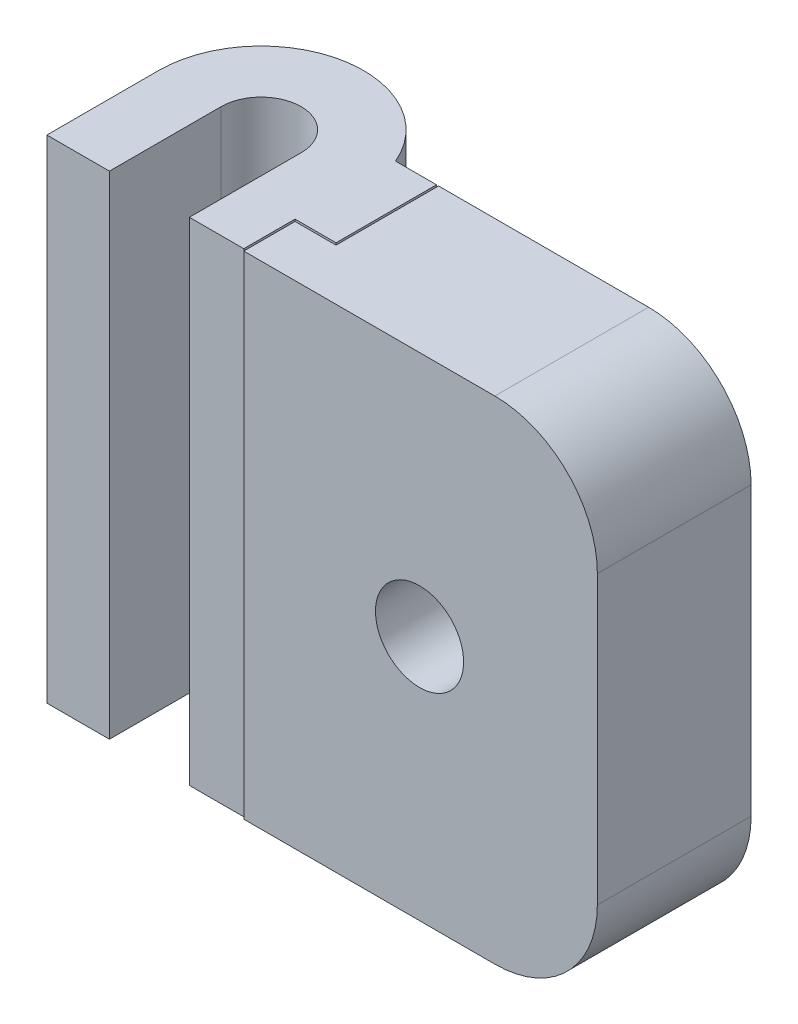
SolidWorks part; units mm, degrees
ref_plane "Front Plane" through (0, 0, 0) normal (0, 0, 1) x (1, 0, 0)
ref_plane "Top Plane" through (0, 0, 0) normal (0, 1, 0) x (1, 0, 0)
ref_plane "Right Plane" through (0, 0, 0) normal (1, 0, 0) x (0, 0, -1)
sketch "Sketch4" plane through (0, 0, 0) normal (0, 1, 0) x (1, 0, 0)
  line L1 (21.95, 0) -> (21.95, 1.95)
  line L2 (21.95, 1.95) -> (4.6041, 1.95)
  line L3 (1.95, 0) -> (1.95, -5.55)
  line L4 (1.95, -5.55) -> (21.95, -5.55)
  line L5 (21.95, -5.55) -> (21.95, 0)
  line L8 (-5, 0) -> (-5, -5.55)
  line L9 (-5, -5.55) -> (-1.95, -5.55)
  line L10 (-1.95, 0) -> (-1.95, -5.55)
  arc A0 (1.95, 0) -> (-1.95, 0) centre (0, 0) ccw
  arc A1 (4.6041, 1.95) -> (-5, 0) centre (0, 0) ccw
  dimension "D1" = 3.9
  dimension "D2" = 10
  dimension "D3" = 5.55
  dimension "D4" = 20
extrude "Boss-Extrude3" add sketch "Sketch4" along normal blind 24
fillet "Fillet1" radius 5 2 edges at (21.95, 0, 1.8) (21.95, 24, 1.8)
sketch "Sketch10" plane through (0, 0, -1.95) normal (0, 0, -1) x (-1, 0, 0)
  line L0 (-21.95, 19) -> (-21.95, 5) construction
  line L2 (-21.95, 12) -> (-4.6041, 12) construction
  line L3 (-4.6041, 24) -> (-4.6041, 0) construction
  circle A0 centre (-13.277, 12) radius 4.1
  point P4 (-21.95, 12)
  point P5 (-13.277, 12)
  dimension "D1" = 8.2
extrude "Cut-Extrude3" cut sketch "Sketch10" against normal blind 3
sketch "Sketch11" plane through (0, 0, 1.05) normal (0, 0, -1) x (-1, 0, 0)
  circle A0 centre (-13.277, 12) radius 2.15
  circle A1 centre (-13.277, 12) radius 4.1
  circle A2 centre (-13.277, 12) radius 4.1 construction
  dimension "D2" = 4.3
  dimension "D1" = 0
extrude "Cut-Extrude4" cut sketch "Sketch11" against normal through all
sketch "Sketch13" plane through (0, 0, 0) normal (0, -1, 0) x (1, 0, 0)
  line L0 (6.6041, -1.95) -> (6.6041, 2.95)
  line L1 (16.95, -1.95) -> (4.6041, -1.95) construction
  line L2 (6.6041, 2.95) -> (4.6041, 2.95)
  line L3 (4.6041, 2.95) -> (4.6041, 5.55)
  line L4 (1.95, 5.55) -> (16.95, 5.55) construction
  line L5 (6.7041, -1.95) -> (6.7041, 3.05)
  line L6 (6.7041, 3.05) -> (4.7041, 3.05)
  line L7 (4.7041, 3.05) -> (4.7041, 5.55)
  line L8 (6.7041, -1.95) -> (6.6041, -1.95)
  line L9 (4.7041, 5.55) -> (4.6041, 5.55)
  dimension "D1" = 2.6
  dimension "D2" = 2
  dimension "D3" = 0.1
extrude "Cut-Extrude5" cut sketch "Sketch13" against normal through all
sketch "Sketch14" plane through (0, 0, 5.55) normal (0, 0, 1) x (1, 0, 0)
  line L4 (-5, 0) -> (-1.95, 0)
  line L5 (-1.95, 0) -> (-1.95, 24)
  line L6 (-1.95, 24) -> (-5, 24)
  line L7 (-5, 24) -> (-5, 0)
  line L8 (-5, 0) -> (-1.95, 0)
  line L9 (-1.95, 0) -> (-1.95, 24)
  line L10 (-1.95, 24) -> (-5, 24)
  line L11 (-5, 24) -> (-5, 0)
  line L12 (1.95, 0) -> (4.6041, 0)
  line L13 (4.6041, 0) -> (4.6041, 24)
  line L14 (4.6041, 24) -> (1.95, 24)
  line L15 (1.95, 24) -> (1.95, 0)
  line L16 (1.95, 0) -> (4.6041, 0)
  line L17 (4.6041, 0) -> (4.6041, 24)
  line L18 (4.6041, 24) -> (1.95, 24)
  line L19 (1.95, 24) -> (1.95, 0)
  dimension "D1" = 0
  dimension "D2" = 0
extrude "Cut-Extrude6" cut sketch "Sketch14" against normal blind 0.1
